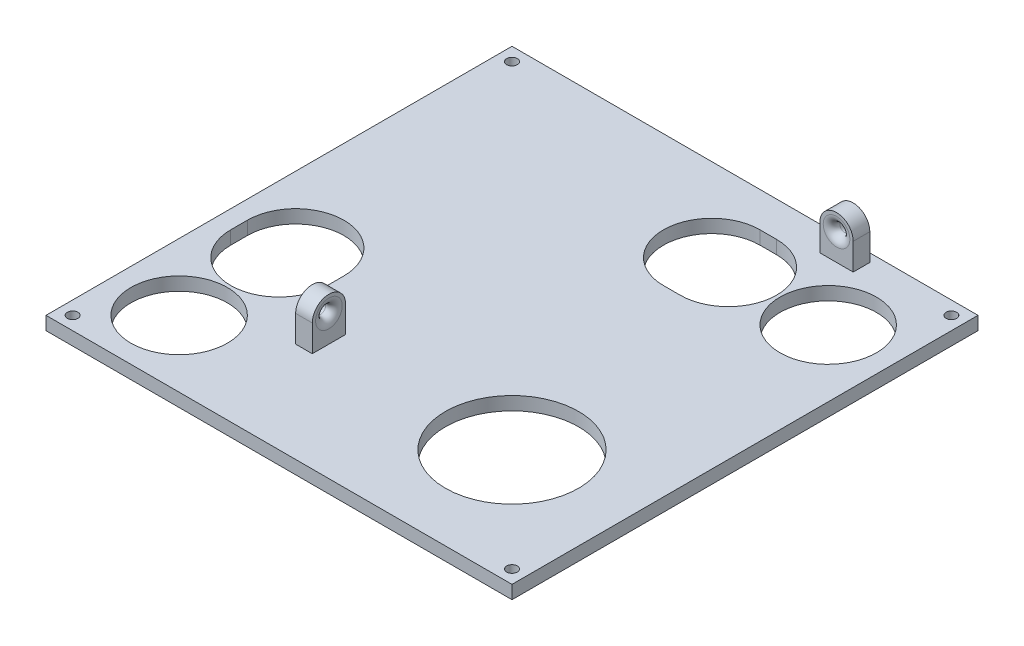
SolidWorks part; units mm, degrees
ref_plane "前视基准面" through (0, 0, 0) normal (0, 0, 1) x (1, 0, 0)
ref_plane "上视基准面" through (0, 0, 0) normal (0, 1, 0) x (1, 0, 0)
ref_plane "右视基准面" through (0, 0, 0) normal (1, 0, 0) x (0, 0, -1)
sketch "Sketch1" plane through (0, 0, 0) normal (0, 1, 0) x (1, 0, 0)
  line L1 (-70, 70) -> (70, 70)
  line L2 (-70, 70) -> (-70, -70)
  line L3 (-70, -70) -> (70, -70)
  line L4 (70, 70) -> (70, -70)
  line L5 (0, -70) -> (0, 70) construction
  line L6 (-70, 0) -> (70, 0) construction
  point P0 (0, 0)
  dimension "D1" = 140
  dimension "D2" = 140
extrude "Boss-Extrude1" add sketch "Sketch1" along normal blind 4
sketch "Sketch2" plane through (0, 4, 0) normal (0, 1, 0) x (1, 0, 0)
  line L0 (70, -70) -> (70, 70) construction
  line L1 (70, 70) -> (-70, 70) construction
  line L2 (-70, -70) -> (70, -70) construction
  line L3 (-70, 70) -> (-70, -70) construction
  line L4 (20, 45) -> (29.5, 45) construction
  line L5 (-50, -20) -> (-50, -29.5) construction
  line L6 (50, 45) -> (59.5, 45) construction
  line L8 (-50, -50) -> (-50, -59.5) construction
  circle A0 centre (50, 45) radius 14.5
  circle A1 centre (20, 45) radius 14.5
  circle A2 centre (-50, -20) radius 14.5
  circle A3 centre (-50, -50) radius 14.5
  circle A5 centre (29.5, 45) radius 1.6 construction
  circle A6 centre (59.5, 45) radius 1.6 construction
  circle A7 centre (-50, -29.5) radius 1.6 construction
  circle A8 centre (-50, -59.5) radius 1.6 construction
  circle A9 centre (20, 35.5) radius 1.6 construction
  circle A10 centre (10.5, 45) radius 1.6 construction
  circle A11 centre (20, 54.5) radius 1.6 construction
  circle A12 centre (50, 35.5) radius 1.6 construction
  circle A13 centre (40.5, 45) radius 1.6 construction
  circle A14 centre (50, 54.5) radius 1.6 construction
  circle A15 centre (-59.5, -50) radius 1.6 construction
  circle A16 centre (-50, -40.5) radius 1.6 construction
  circle A17 centre (-40.5, -50) radius 1.6 construction
  circle A19 centre (-59.5, -20) radius 1.6 construction
  circle A21 centre (-50, -10.5) radius 1.6 construction
  circle A23 centre (-40.5, -20) radius 1.6 construction
  circle A24 centre (-10.5, -20) radius 1.6 [skipped]
  circle A25 centre (-89.5, -20) radius 1.6 [skipped]
  circle A26 centre (-50, 19.5) radius 1.6 [skipped]
  point P33 (20, 45)
  point P40 (50, 45)
  point P47 (-50, -50)
  point P60 (-50, -20)
  dimension "D1" = 29
  dimension "D8" = 3.2
  dimension "D11" = 3.2
  dimension "D2" = 20
  dimension "D3" = 25
  dimension "D4" = 20
  dimension "D5" = 20
  dimension "D6" = 30
  dimension "D7" = 30
  dimension "D9" = 9.5
  dimension "D10" = 9.5
  dimension "D12" = 9.5
  dimension "D13" = 4
  dimension "D14" = 4
  dimension "D15" = 4
  dimension "D16" = 4
extrude "Cut-Extrude1" cut sketch "Sketch2" against normal blind 4
sketch "Sketch3" plane through (0, 4, 0) normal (0, 1, 0) x (1, 0, 0)
  line L0 (-50, -20) -> (-50, -50) construction
  line L2 (20, 45) -> (50, 45) construction
  line L4 (-50, -35) -> (35, -35) construction
  line L5 (35, -35) -> (35, 45) construction
  circle A0 centre (35, -35) radius 20
  circle A1 centre (35, -23.75) radius 1.6 construction
  circle A2 centre (46.25, -35) radius 1.6 construction
  circle A3 centre (35, -46.25) radius 1.6 construction
  circle A4 centre (23.75, -35) radius 1.6 construction
  point P14 (0, 0)
  point P15 (0, 0)
  point P16 (0, 0)
  point P23 (35, -35)
  point P24 (0, 0)
  point P25 (50, 40)
  point P27 (20, 40)
  point P29 (-50, -40)
  point P31 (-50, -10)
  dimension "D1" = 40
  dimension "D2" = 11.25
  dimension "D3" = 3.2
  dimension "D4" = 4
extrude "Cut-Extrude2" cut sketch "Sketch3" against normal blind 10
sketch "Sketch5" plane through (0, 4, 0) normal (0, 1, 0) x (1, 0, 0)
  line L0 (-70, -70) -> (70, -70) construction
  line L1 (-66, -66) -> (66, -66) construction
  line L2 (-66, -66) -> (-66, 66) construction
  line L3 (-66, 66) -> (66, 66) construction
  line L4 (66, -66) -> (66, 66) construction
  line L5 (0, 66) -> (0, -66) construction
  line L6 (-66, 0) -> (66, 0) construction
  line L7 (-70, 70) -> (-70, -70) construction
  circle A0 centre (-66, 66) radius 1.6
  circle A1 centre (66, 66) radius 1.6
  circle A2 centre (66, -66) radius 1.6
  circle A3 centre (-66, -66) radius 1.6
  point P0 (0, 0)
  dimension "D1" = 3.2
  dimension "D2" = 4
  dimension "D3" = 4
extrude "Cut-Extrude5" cut sketch "Sketch5" against normal blind 10
sketch "Sketch7" plane through (0, 4, 0) normal (0, 1, 0) x (1, 0, 0)
  line L0 (-50, -20) -> (-50, -15) construction
  line L1 (-64.5, -20) -> (-64.5, -15)
  line L2 (-35.5, -20) -> (-35.5, -15)
  line L3 (20, 45) -> (15, 45) construction
  line L4 (20, 30.5) -> (15, 30.5)
  line L5 (20, 59.5) -> (15, 59.5)
  arc A0 (-64.5, -20) -> (-35.5, -20) centre (-50, -20) ccw
  arc A1 (-35.5, -15) -> (-64.5, -15) centre (-50, -15) ccw
  arc A2 (20, 30.5) -> (20, 59.5) centre (20, 45) ccw
  arc A3 (15, 59.5) -> (15, 30.5) centre (15, 45) ccw
  circle A4 centre (-50, -20) radius 14.5 construction
  point P3 (-50, -17.5)
  point P10 (17.5, 45)
  dimension "D1" = 5
extrude "Cut-Extrude6" cut sketch "Sketch7" against normal blind 10
sketch "Sketch8" plane through (0, 4, 0) normal (0, 1, 0) x (1, 0, 0)
  line L0 (-50, -50) -> (-50, -20) construction
  line L2 (20, 45) -> (50, 45) construction
  line L3 (-25, -30) -> (-20, -30)
  line L4 (-25, -30) -> (-25, -40)
  line L5 (-25, -40) -> (-20, -40)
  line L6 (-20, -30) -> (-20, -40)
  line L7 (-22.5, -40) -> (-22.5, -30) construction
  line L8 (-25, -35) -> (-20, -35) construction
  line L9 (30, 67.5) -> (40, 67.5)
  line L10 (30, 67.5) -> (30, 62.5)
  line L11 (30, 62.5) -> (40, 62.5)
  line L12 (40, 67.5) -> (40, 62.5)
  line L13 (35, 62.5) -> (35, 67.5) construction
  line L14 (30, 65) -> (40, 65) construction
  point P4 (-22.5, -35)
  point P12 (35, 65)
  point P19 (0, 0)
  point P20 (-50, -35)
  point P21 (0, 0)
  point P22 (35, 45)
  dimension "D1" = 5
  dimension "D2" = 10
  dimension "D3" = 22.5
  dimension "D4" = 25
extrude "Boss-Extrude2" add sketch "Sketch8" along normal blind 14
sketch "Sketch9" plane through (0, 0, -62.5) normal (0, 0, 1) x (1, 0, 0)
  line L0 (-70, 4) -> (70, 4) construction
  line L1 (35, 18) -> (35, 12) construction
  line L2 (30, 18) -> (40, 18) construction
  line L3 (30, 18) -> (30, 4) construction
  line L4 (40, 18) -> (40, 4) construction
  line L5 (30, 12) -> (30, 22.099)
  line L6 (30, 22.099) -> (40, 22.099)
  line L7 (40, 22.099) -> (40, 12)
  circle A0 centre (35, 12) radius 1.5
  arc A1 (30, 12) -> (40, 12) centre (35, 12) cw
  dimension "D1" = 8
  dimension "D2" = 3
extrude "Cut-Extrude7" cut sketch "Sketch9" against normal through all
sketch "Sketch10" plane through (-20, 0, 0) normal (1, 0, 0) x (0, 0, -1)
  line L0 (-40, 18) -> (-40, 4) construction
  line L1 (-30, 18) -> (-30, 4) construction
  line L2 (-70, 4) -> (70, 4) construction
  line L3 (-40, 12) -> (-40, 23.5311)
  line L4 (-40, 23.5311) -> (-30, 23.5311)
  line L5 (-30, 23.5311) -> (-30, 12)
  circle A0 centre (-35, 12) radius 1.5
  arc A1 (-40, 12) -> (-30, 12) centre (-35, 12) cw
  point P13 (-35, 23.5311)
  dimension "D1" = 3
  dimension "D2" = 8
extrude "Cut-Extrude8" cut sketch "Sketch10" against normal blind 5
fillet "Fillet1" radius 2.5 4 edges at (36.5, 12, -67.5) (36.5, 12, -62.5) (-25, 12, 33.5) (-20, 12, 33.5)
equation "\"D4@Sketch2\"=\"D5@Sketch2\""
equation "\"D2@Sketch2\"=\"D5@Sketch2\""
equation "\"D3@Sketch5\"=\"D2@Sketch5\""
